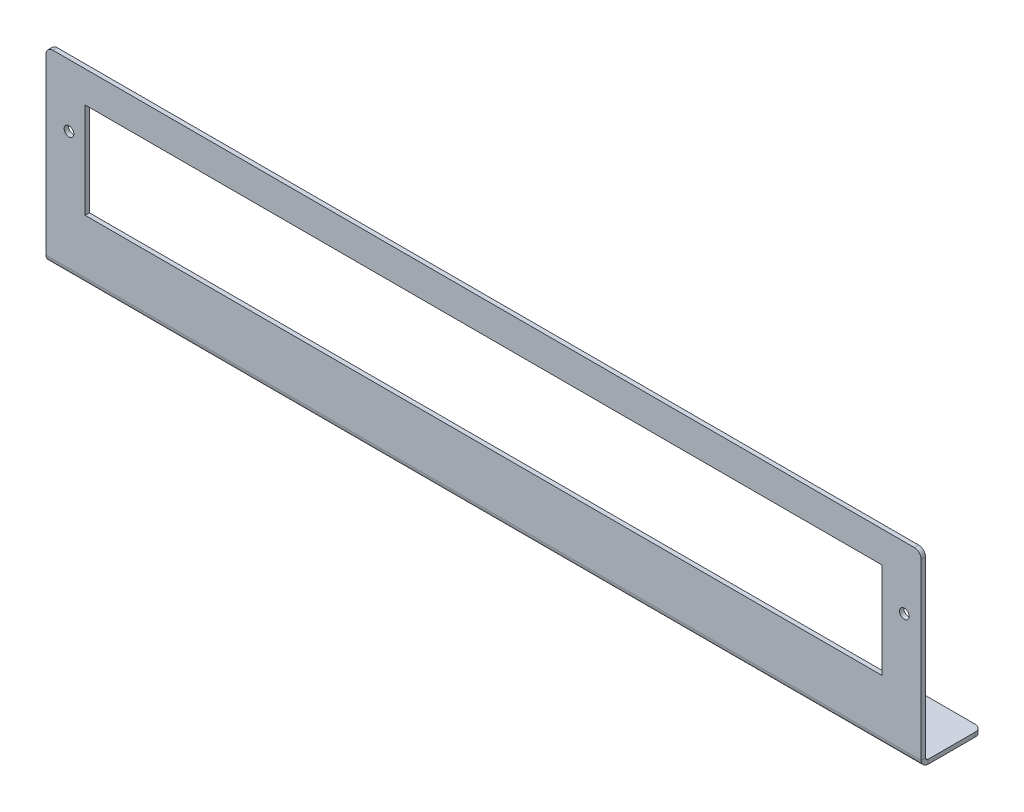
SolidWorks part; units mm, degrees
note: The reader was unsure of these and kept them because the rebuilt part matched: flange length of "Edge-Flange1".
material "6061 Alloy"
ref_plane "Front" through (0, 0, 0) normal (0, 0, 1) x (1, 0, 0)
ref_plane "Top" through (0, 0, 0) normal (0, 1, 0) x (1, 0, 0)
ref_plane "Right" through (0, 0, 0) normal (1, 0, 0) x (0, 0, -1)
sketch "Sketch2" plane through (0, 0, 0) normal (0, 0, 1) x (1, 0, 0)
  line L1 (127.88, 27.43) -> (-127.88, 27.43)
  line L2 (127.88, 27.43) -> (127.88, -27.43)
  line L3 (127.88, -27.43) -> (-127.88, -27.43)
  line L4 (-127.88, 27.43) -> (-127.88, -27.43)
  line L5 (127.88, 27.43) -> (-127.88, -27.43) construction
  line L6 (127.88, -27.43) -> (-127.88, 27.43) construction
  line L7 (-116.45, 18.29) -> (116.45, 18.29)
  line L8 (-116.45, 18.29) -> (-116.45, -9.65)
  line L9 (-116.45, -9.65) -> (116.45, -9.65)
  line L10 (116.45, 18.29) -> (116.45, -9.65)
  point P0 (0, 0)
  dimension "D1" = 255.76
  dimension "D2" = 54.86
  dimension "D3" = 11.43
  dimension "D4" = 232.9
  dimension "D5" = 27.94
  dimension "D6" = 9.14
base flange "Base-Flange1" sketch "Sketch2" thickness 1.27 reverse thickness direction no parameters "D1"=0.7366
edge flange "Edge-Flange1" sketch "Sketch9" flange angle 90 flange length 17.78 flange position material inside bend radius 0.7366 thickness 1.27 relief rectangular parameters "D6"=10
sketch "Sketch9" plane through (0, -27.43, -1.27) normal (0, 1, 0) x (1, 0, 0)
  line L2 (-127.88, 0) -> (-127.88, 16.51)
  line L3 (-127.88, 16.51) -> (127.88, 16.51)
  line L4 (127.88, 16.51) -> (127.88, 0)
  line L13 (127.88, 0) -> (-127.88, 0) construction
  line L14 (127.88, 0) -> (-127.88, 0)
bend "EdgeBend1" bend radius 0.7366 bend angle 90 parameters "D5"=1
hole_wizard "#34 (0.111) Diameter Hole1" positions "Sketch10" profile "Sketch11" hole size "#34" standard "ANSI Inch" end condition through all
sketch "Sketch10" plane through (0, 0, -1.27) normal (0, 0, -1) x (-1, 0, 0)
  line L0 (-127.88, -25.4234) -> (-127.88, 27.43) construction
  line L1 (-127.88, 27.43) -> (127.88, 27.43) construction
  point P0 (-122.95, 9.24)
  point P2 (121.16, 9.24)
  dimension "D1" = 4.93
  dimension "D2" = 18.19
  dimension "D3" = 244.11
sketch "Sketch11" plane through (122.95, 9.24, -1.27) normal (1, 0, 0) x (0, 1, 0)
  line L0 (0, 0) -> (0, 1.27)
  line L1 (0, 1.27) -> (1.4097, 1.27)
  line L2 (1.4097, 1.27) -> (1.4097, 0)
  line L5 (1.4097, 0) -> (0, 0)
  line L11 (0, -6.35) -> (0, 107.95) construction
  dimension "Thru Hole Dia." = 2.8194
  dimension "Thru Hole Depth" = 1.27
fillet "Fillet1" radius 2 4 edges at (-127.88, -26.795, -17.78) (-127.88, 27.43, -0.635) (127.88, -26.795, -17.78) (127.88, 27.43, -0.635)
sketch "Bend-Lines1" [suppressed] plane through (0, 0, 0) normal (0, 1, 0) x (1, 0, 0)
sketch "Bounding-Box1" [suppressed] plane through (0, 0, 0) normal (0, 1, 0) x (1, 0, 0)
sheet metal parameters "Sheet-Metal2" thickness 1.27 parameters "D1"=0.7366
flat pattern "Flat-Pattern2" [suppressed]
sketch "Bend-Lines2" plane through (0, 0, 0) normal (0, 1, 0) x (1, 0, 0)
sketch "Bounding-Box2" [suppressed] plane through (0, 0, 0) normal (0, 1, 0) x (1, 0, 0)
sheet metal parameters "Sheet-Metal3" thickness 1.27 parameters "D1"=0.7366
flat pattern "Flat-Pattern2" [suppressed]
sketch "Bend-Lines2" plane through (0, 0, 0) normal (0, 1, 0) x (1, 0, 0)
sketch "Bounding-Box2" [suppressed] plane through (0, 0, 0) normal (0, 1, 0) x (1, 0, 0)
bend of the flat pattern "Flatten-<EdgeBend1>1"
sheet metal parameters "Sheet-Metal4" thickness 1.27 parameters "D1"=0.7366
flat pattern "Flat-Pattern2"
sketch "Bend-Lines2" plane through (0, 0, 0) normal (0, 0, 1) x (1, 0, 0)
  line L0 (-127.88, -26.5007) -> (127.88, -26.5007) construction
  line L1 (-127.88, -26.5007) -> (127.88, -26.5007) construction
sketch3d "Bounding-Box2" [suppressed]
  line L0 (-127.88, 27.4301, 0) -> (127.88, 27.43, 0) construction
  line L1 (-127.88, -43.3512, 0) -> (127.88, -43.3513, 0) construction
  line L2 (-127.88, 27.4301, 0) -> (-127.88, -43.3512, 0) construction
  line L3 (127.88, 27.43, 0) -> (127.88, -43.3513, 0) construction
bend of the flat pattern "Flatten-<EdgeBend1>1"
